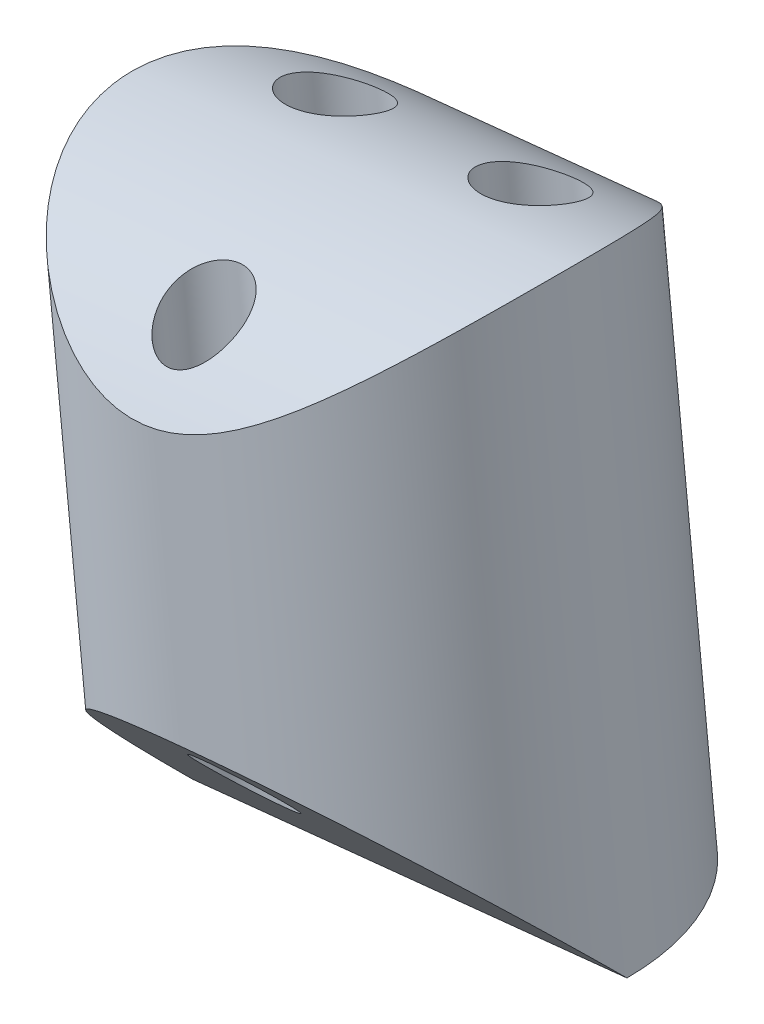
SolidWorks part; units mm, degrees
ref_plane "Front Plane" through (0, 0, 0) normal (0, 0, 1) x (1, 0, 0)
ref_plane "Top Plane" through (0, 0, 0) normal (0, 1, 0) x (1, 0, 0)
ref_plane "Right Plane" through (0, 0, 0) normal (1, 0, 0) x (0, 0, -1)
sketch "Sketch2" plane through (0, 0, 0) normal (0, 0, 1) x (1, 0, 0)
  line L0 (0, 0) -> (90, 0)
  line L1 (90, 0) -> (90, 120)
  line L2 (90, 120) -> (0, 120)
  line L3 (0, 120) -> (0, 0)
  line L4 (0, 120) -> (-10, 120)
  line L5 (-10, 120) -> (-10, 16.9491)
  line L6 (-10, 120) -> (57.5, 127)
  line L7 (57.5, 127) -> (90, 124)
  line L8 (90, 120) -> (99, 60)
  line L10 (90, 124) -> (90, 120)
  line L11 (5.9147, 0) -> (5.9147, -25)
  line L12 (5.9147, -25) -> (-4.0853, -25)
  line L13 (-4.0853, -29) -> (-4.0853, 0)
  line L14 (80, 0) -> (80, -25)
  line L15 (80, -25) -> (90, -25)
  line L16 (90, -29) -> (90, 0)
  line L17 (15.7927, 122.6748) -> (5.4776, 222.1414)
  line L18 (5.4776, 222.1414) -> (21.3923, 223.7918)
  line L19 (21.3923, 223.7918) -> (31.7073, 124.3252)
  line L20 (7.6492, 201.201) -> (23.5639, 202.8514)
  line L21 (10.9066, 169.7905) -> (26.8212, 171.441)
  line L22 (-10, 120) -> (-20.0396, 216.8108)
  line L23 (-20.0396, 216.8108) -> (-4.125, 218.4612)
  line L24 (-4.125, 218.4612) -> (5.9147, 121.6504)
  line L25 (-17.926, 196.4296) -> (-2.0114, 198.08)
  line L26 (-14.7556, 165.8578) -> (1.159, 167.5082)
  line L27 (57.5, 127) -> (46.9095, 229.1223)
  line L28 (46.9095, 229.1223) -> (30.9949, 227.4719)
  line L29 (30.9949, 227.4719) -> (41.5853, 125.3496)
  line L30 (33.2245, 205.9725) -> (49.1391, 207.6229)
  line L31 (36.5688, 173.7233) -> (52.4835, 175.3737)
  line L34 (90, 124) -> (99.1917, 223.5767)
  line L35 (99.1917, 223.5767) -> (83.2594, 225.0473)
  line L36 (83.2594, 225.0473) -> (74.0677, 125.4707)
  line L38 (81.3243, 204.0838) -> (97.2566, 202.6132)
  line L39 (78.4217, 172.6386) -> (94.354, 171.1679)
  line L40 (62.4078, 79.6749) -> (57.5, 127) construction
  line L41 (41.5853, 125.3496) -> (46.4931, 78.0244) construction
  line L42 (46.4931, 78.0244) -> (62.4078, 79.6749) construction
  line L43 (31.7073, 124.3252) -> (36.6151, 77.0001) construction
  line L44 (36.6151, 77.0001) -> (20.7005, 75.3496) construction
  line L45 (20.7005, 75.3496) -> (15.7927, 122.6748) construction
  line L46 (5.9147, 121.6504) -> (10.8224, 74.3253) construction
  line L47 (10.8224, 74.3253) -> (-5.0922, 72.6749) construction
  line L48 (-5.0922, 72.6749) -> (-10, 120) construction
  line L49 (74.0677, 125.4707) -> (69.6944, 78.0931) construction
  line L50 (69.6944, 78.0931) -> (85.7624, 78.0931) construction
  line L51 (85.7624, 78.0931) -> (90, 124) construction
  line L52 (-12.0823, 217.636) -> (10.4873, 0) construction
  line L53 (13.4349, 222.9666) -> (36.5574, 0) construction
  line L54 (38.9522, 228.2971) -> (62.6275, 0) construction
  line L55 (91.2256, 224.312) -> (70.5198, 0) construction
  line L59 (99, 60) -> (93.5277, 44.9649)
  line L60 (99, 60) -> (169.4769, 34.3485)
  line L61 (169.4769, 34.3485) -> (164.0046, 19.3134)
  line L62 (164.0046, 19.3134) -> (93.5277, 44.9649)
  line L63 (90, -2) -> (100, -2)
  line L64 (141.2862, 44.6091) -> (135.8138, 29.574)
  line L65 (99, 60) -> (55.7741, 75.7329) construction
  line L66 (55.7741, 75.7329) -> (50.3018, 60.6978) construction
  line L67 (100, -2) -> (100, -29)
  line L70 (-4.0853, -2) -> (-14.0853, -2)
  line L71 (-14.0853, -2) -> (-14.0853, -29)
  line L74 (-4.0853, 0) -> (0, 0)
  line L75 (-14.0853, -29) -> (-14.0853, -112.587)
  line L76 (-14.0853, -112.587) -> (100, -112.587)
  line L77 (100, -112.587) -> (100, -29)
  line L78 (-14.0853, -29) -> (100, -29)
  line L79 (-14.0853, -14.5) -> (100, -14.5) construction
  line L80 (31.7073, -112.587) -> (31.7073, -122.6232)
  line L81 (31.7073, -122.6232) -> (42.9573, -122.6232)
  line L82 (42.9573, -122.6232) -> (42.9573, -112.587)
  line L83 (-14.0853, -112.587) -> (-88.3667, -112.587)
  line L84 (-88.3667, -112.587) -> (-88.3667, -128.2699)
  line L85 (-88.3667, -128.2699) -> (169.4958, -128.2699)
  line L86 (169.4958, -128.2699) -> (169.4958, -112.587)
  line L87 (169.4958, -112.587) -> (100, -112.587)
  line L88 (90, 60) -> (-10, 60) construction
  line L89 (50.3018, 60.6978) -> (93.5277, 44.9649) construction
  line L90 (87.2806, 55.7521) -> (166.7408, 26.8309) construction
  line L91 (87.2806, 55.7521) -> (82.1749, 52.5336) construction
  line L92 (82.1749, 52.5336) -> (77.3257, 0) construction
  line L93 (83.1185, 56.6957) -> (86.337, 51.59) construction
  arc A0 (-10, 16.9491) -> (-4.0853, 0) centre (14.9876, 16.1624) ccw
  arc A1 (93.5277, 44.9649) -> (90, 0) centre (-126.4069, 39.5988) cw
  point P42 (41.1818, 206.7977)
  point P100 (84.7278, 54.1428)
  point P101 (84.7278, 54.1428)
  dimension "D11" = 47.3684
  dimension "D35" = 9
  dimension "D32" = 220
  dimension "D36" = 25
  dimension "D1" = 120
  dimension "D2" = 90
  dimension "D3" = 10
  dimension "D5" = 67.862
  dimension "D6" = 7
  dimension "D7" = 4
  dimension "D8" = 16
  dimension "D9" = 16
  dimension "D10" = 100
  dimension "D12" = 31.5789
  dimension "D13" = 16
  dimension "D14" = 16
  dimension "D15" = 16
  dimension "D16" = 25.7927
  dimension "D17" = 100
  dimension "D18" = 21.0526
  dimension "D19" = 31.5789
  dimension "D20" = 97.33
  dimension "D21" = 102.67
  dimension "D22" = 20.4905
  dimension "D23" = 30.7358
  dimension "D24" = 21.6147
  dimension "D25" = 32.4221
  dimension "D26" = 25
  dimension "D28" = 25
  dimension "D29" = 75
  dimension "D30" = 47.5789
  dimension "D31" = 30
  dimension "D33" = 46
  dimension "D34" = 20
  dimension "D37" = 2
  dimension "D38" = 2
  dimension "D39" = 27
  dimension "D40" = 10
  dimension "D41" = 10
  dimension "D42" = 27
  dimension "D43" = 14.5
  dimension "D44" = 127.5
ref_plane "Plane1" through (87.2806, 55.7521, 0) normal (-0.846, -0.5333, 0) x (0, 0, 1)
ref_plane "Plane2" through (82.1749, 52.5336, 0) normal (-0.0919, -0.9958, 0) x (-0.9958, 0.0919, 0)
ref_plane "Plane3" through (91.2256, 224.312, 0) normal (-0.0919, -0.9958, 0) x (-0.9958, 0.0919, 0)
ref_plane "Plane4" through (38.9522, 228.2971, 0) normal (0.1032, -0.9947, 0) x (-0.9947, -0.1032, 0)
ref_plane "Plane5" through (13.4349, 222.9666, 0) normal (0.1032, -0.9947, 0) x (-0.9947, -0.1032, 0)
ref_plane "Plane7" through (166.7408, 26.8309, 0) normal (0.9397, -0.342, 0) x (0, 0, -1)
ref_plane "Plane8" through (110.4217, -40.1902, 0) normal (0.9397, -0.342, 0) x (0, 0, -1)
ref_plane "Plane9" through (19.3664, 209.803, 0) normal (-0.0919, -0.9958, 0) x (-0.9958, 0.0919, 0)
ref_plane "Plane10" through (16.4638, 178.3578, 0) normal (-0.0919, -0.9958, 0) x (-0.9958, 0.0919, 0)
ref_plane "Plane11" through (-20.7793, 200.3721, 0) normal (0.1032, -0.9947, 0) x (-0.9947, -0.1032, 0)
ref_plane "Plane12" through (-17.435, 168.1229, 0) normal (0.1032, -0.9947, 0) x (-0.9947, -0.1032, 0)
ref_plane "Plane13" through (-20.5619, 198.2754, 0) normal (0.1032, -0.9947, 0) x (-0.9947, -0.1032, 0)
ref_plane "Plane14" through (-17.3045, 166.8649, 0) normal (0.1032, -0.9947, 0) x (-0.9947, -0.1032, 0)
ref_plane "Plane15" through (-12.0823, 217.636, 0) normal (0.1032, -0.9947, 0) x (-0.9947, -0.1032, 0)
ref_plane "Plane16" through (-20.3445, 196.1788, 0) normal (0.1032, -0.9947, 0) x (-0.9947, -0.1032, 0)
ref_plane "Plane17" through (-17.1741, 165.607, 0) normal (0.1032, -0.9947, 0) x (-0.9947, -0.1032, 0)
ref_plane "Plane18" through (12.1098, 131.1899, 0) normal (-0.0919, -0.9958, 0) x (-0.9958, 0.0919, 0)
ref_plane "Plane19" through (-12.4184, 119.7492, 0) normal (0.1032, -0.9947, 0) x (-0.9947, -0.1032, 0)
ref_plane "Plane20" through (0, 0, 0) normal (0, 0, 1) x (0.1032, -0.9947, 0)
ref_plane "Plane21" through (0, 0, 0) normal (0, 0, 1) x (-0.0919, -0.9958, 0)
ref_plane "Plane22" through (10.3758, 1.076, 0) normal (-0.9947, -0.1032, 0) x (0.1032, -0.9947, 0)
ref_plane "Plane23" through (36.1684, 3.7508, 0) normal (-0.9947, -0.1032, 0) x (0.1032, -0.9947, 0)
ref_plane "Plane24" through (61.9611, 6.4256, 0) normal (-0.9947, -0.1032, 0) x (0.1032, -0.9947, 0)
ref_plane "Plane25" through (69.924, -6.4545, 0) normal (-0.9958, 0.0919, 0) x (-0.0919, -0.9958, 0)
sketch "Sketch3" plane through (-12.0823, 217.636, 0) normal (0.1032, -0.9947, 0) x (-0.9947, -0.1032, 0)
  circle A0 centre (0, 0) radius 8
  dimension "D1" = 16
extrude "Boss-Extrude1" add sketch "Sketch3" along normal blind 21.6147
sketch "Sketch4" plane through (10.3758, 1.076, 0) normal (-0.9947, -0.1032, 0) x (0.1032, -0.9947, 0)
  line L0 (-217.7214, 8) -> (-213.7214, 8)
  line L1 (-196.1067, 8) -> (-217.7214, 8) construction
  line L2 (-217.7214, 8) -> (-217.7214, -8)
  line L3 (-217.7214, -8) -> (-213.7214, -8)
  line L4 (-217.7214, -8) -> (-196.1067, -8) construction
  arc A0 (-213.7214, 8) -> (-213.7214, -8) centre (-207.3937, 0) ccw
  dimension "D2" = 10.2
  dimension "D1" = 4
extrude "Cut-Extrude1" cut sketch "Sketch4" against normal through all and the other way through all
sketch "Sketch5" plane through (10.3758, 1.076, 0) normal (-0.9947, -0.1032, 0) x (0.1032, -0.9947, 0)
  line L0 (-196.1067, 0) -> (-204.1067, 8)
  line L1 (-196.1067, -8) -> (-196.1067, 8) construction
  line L2 (-196.1067, 8) -> (-213.7214, 8) construction
  line L3 (-204.1067, 8) -> (-196.1067, 8)
  line L4 (-196.1067, 8) -> (-196.1067, 0)
  dimension "D1" = 45
extrude "Cut-Extrude2" cut sketch "Sketch5" against normal through all and the other way through all
sketch "Sketch7" plane through (10.3758, 1.076, 0) normal (-0.9947, -0.1032, 0) x (0.1032, -0.9947, 0)
  line L2 (-192.1067, 0) -> (-196.1067, -4)
  line L5 (-200.1067, 4) -> (-196.1067, 0)
  line L6 (-196.1067, 0) -> (-204.1067, 8) construction
  line L8 (-213.7055, 0) -> (7.2742, 0) construction
  line L9 (-192.1067, 0) -> (-192.1067, 4)
  line L10 (-192.1067, 4) -> (-200.1067, 4)
  line L11 (-196.1067, 0) -> (-192.1067, 4) construction
  line L12 (-196.1067, -8) -> (-196.1067, 0) construction
  line L13 (-196.1067, 0) -> (-196.1067, -4)
  dimension "D1" = 45
sketch "Sketch8" plane through (-12.0823, 217.636, 0) normal (0.1032, -0.9947, 0) x (-0.9947, -0.1032, 0)
  line L0 (8, 0) -> (-8, 0) construction
  circle A0 centre (-3.6, 3) radius 1.6
  circle A1 centre (3.6, 3) radius 1.6
  circle A3 centre (0, -5.5) radius 1.4
  point P6 (0, 0)
  dimension "D1" = 3.2
  dimension "D2" = 3.2
  dimension "D7" = 2.8
  dimension "D3" = 3
  dimension "D4" = 3
  dimension "D5" = 3.6
  dimension "D6" = 3.6
  dimension "D8" = 5.5
extrude "Cut-Extrude3" cut sketch "Sketch8" against normal through all and the other way through all
sketch "Sketch9" plane through (-20.2285, 195.0606, 0) normal (0.1032, -0.9947, 0) x (0.9947, 0.1032, 0)
  line L0 (4.5289, -5.4) -> (16.3339, -5.4)
  line L1 (2.4314, 0) -> (18.4314, 0) construction
  arc A0 (2.4314, 0) -> (18.4314, 0) centre (10.4314, 0) ccw construction
  arc A1 (4.5289, -5.4) -> (16.3339, -5.4) centre (10.4314, 0) ccw
  dimension "D1" = 5.4
